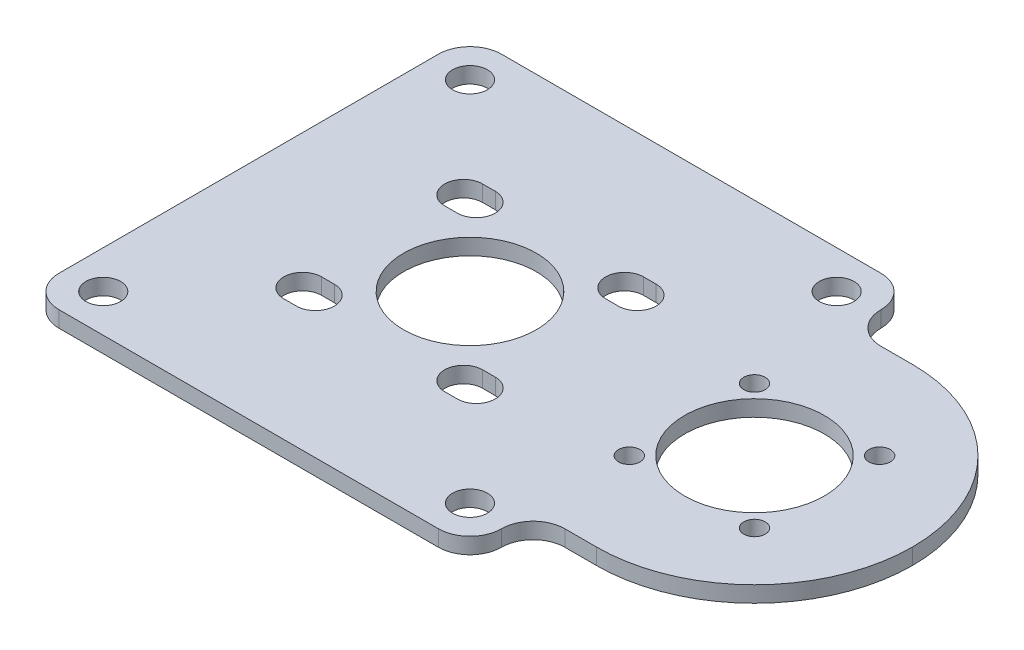
SolidWorks part; units mm, degrees
material "1060 Alloy"
ref_plane "Front Plane" through (0, 0, 0) normal (0, 0, 1) x (1, 0, 0)
ref_plane "Top Plane" through (0, 0, 0) normal (0, 1, 0) x (1, 0, 0)
ref_plane "Right Plane" through (0, 0, 0) normal (1, 0, 0) x (0, 0, -1)
sketch "Sketch1" plane through (0, 0, 0) normal (0, 1, 0) x (1, 0, 0)
  line L0 (0, 0) -> (0, 70)
  line L9 (0, 35) -> (35, 35) construction
  line L10 (35, 35) -> (22.2721, 47.7279) construction
  line L37 (35, 35) -> (35, 53) construction
  line L38 (0, 70) -> (70, 70)
  line L39 (0, 0) -> (70, 0)
  line L41 (80, 35) -> (80, 49) construction
  line L48 (80, 35) -> (70.1005, 44.8995) construction
  line L49 (70, 70) -> (70, 60)
  line L50 (70, 0) -> (70, 10)
  line L51 (70, 60) -> (105, 60)
  line L52 (70, 10) -> (105, 10)
  line L53 (105, 60) -> (105, 10)
  line L54 (21.2721, 47.7279) -> (23.2721, 47.7279) construction
  line L55 (21.2721, 50.7279) -> (23.2721, 50.7279)
  line L56 (21.2721, 44.7279) -> (23.2721, 44.7279)
  line L57 (48.7279, 47.7279) -> (46.7279, 47.7279) construction
  line L58 (48.7279, 50.7279) -> (46.7279, 50.7279)
  line L59 (48.7279, 44.7279) -> (46.7279, 44.7279)
  line L60 (21.2721, 22.2721) -> (23.2721, 22.2721) construction
  line L61 (21.2721, 19.2721) -> (23.2721, 19.2721)
  line L62 (21.2721, 25.2721) -> (23.2721, 25.2721)
  line L63 (48.7279, 22.2721) -> (46.7279, 22.2721) construction
  line L64 (48.7279, 19.2721) -> (46.7279, 19.2721)
  line L65 (48.7279, 25.2721) -> (46.7279, 25.2721)
  circle A19 centre (35, 35) radius 10.5
  circle A20 centre (35, 35) radius 18 construction
  circle A25 centre (80, 35) radius 11.05
  circle A26 centre (80, 35) radius 14 construction
  circle A27 centre (70.1005, 44.8995) radius 1.7
  circle A28 centre (89.8995, 44.8995) radius 1.7
  circle A29 centre (89.8995, 25.1005) radius 1.7
  circle A30 centre (70.1005, 25.1005) radius 1.7
  arc A31 (21.2721, 50.7279) -> (21.2721, 44.7279) centre (21.2721, 47.7279) ccw
  arc A32 (23.2721, 44.7279) -> (23.2721, 50.7279) centre (23.2721, 47.7279) ccw
  arc A33 (48.7279, 50.7279) -> (48.7279, 44.7279) centre (48.7279, 47.7279) cw
  arc A34 (46.7279, 44.7279) -> (46.7279, 50.7279) centre (46.7279, 47.7279) cw
  arc A35 (21.2721, 19.2721) -> (21.2721, 25.2721) centre (21.2721, 22.2721) cw
  arc A36 (23.2721, 25.2721) -> (23.2721, 19.2721) centre (23.2721, 22.2721) cw
  arc A37 (48.7279, 19.2721) -> (48.7279, 25.2721) centre (48.7279, 22.2721) ccw
  arc A38 (46.7279, 25.2721) -> (46.7279, 19.2721) centre (46.7279, 22.2721) ccw
  point P6 (18.2721, 47.7279)
  point P14 (26.2721, 47.7279)
  point P15 (0, 0)
  point P21 (47.7279, 47.7279)
  point P23 (35, 35)
  point P39 (80, 35)
  point P42 (22.2721, 47.7279)
  point P52 (22.2721, 22.2721)
  point P60 (47.7279, 22.2721)
  dimension "D4" = 36
  dimension "D9" = 28
  dimension "D7" = 70
  dimension "D1" = 70
  dimension "D2" = 35
  dimension "D8" = 22.1
  dimension "D11" = 45
  dimension "D13" = 50
  dimension "D14" = 25
  dimension "D15" = 8
  dimension "D3" = 21
  dimension "D6" = 6
  dimension "D12" = 3.4
  dimension "D5" = 45
  dimension "D10" = 45
extrude "Boss-Extrude1" add sketch "Sketch1" along normal blind 2.54
fillet "Fillet1" radius 25 2 edges at (105, 1.27, -10) (105, 1.27, -60)
fillet "Fillet2" radius 5 6 edges at (70, 1.27, -60) (70, 1.27, -10) (0, 1.27, -70) (0, 1.27, 0) (70, 1.27, 0) (70, 1.27, -70)
sketch "Sketch2" plane through (0, 2.54, 0) normal (0, 1, 0) x (1, 0, 0)
  line L0 (0, 65) -> (0, 5) construction
  line L1 (6, 64) -> (64, 64) construction
  line L2 (6, 64) -> (6, 6) construction
  line L3 (6, 6) -> (64, 6) construction
  line L4 (64, 64) -> (64, 6) construction
  line L5 (65, 70) -> (5, 70) construction
  line L6 (5, 0) -> (65, 0) construction
  circle A0 centre (6, 64) radius 2.75
  circle A2 centre (64, 64) radius 2.75
  circle A3 centre (64, 6) radius 2.75
  circle A4 centre (6, 6) radius 2.75
  dimension "D1" = 5.5
  dimension "D2" = 6
  dimension "D3" = 6
  dimension "D4" = 6
extrude "Cut-Extrude1" cut sketch "Sketch2" against normal blind 10
